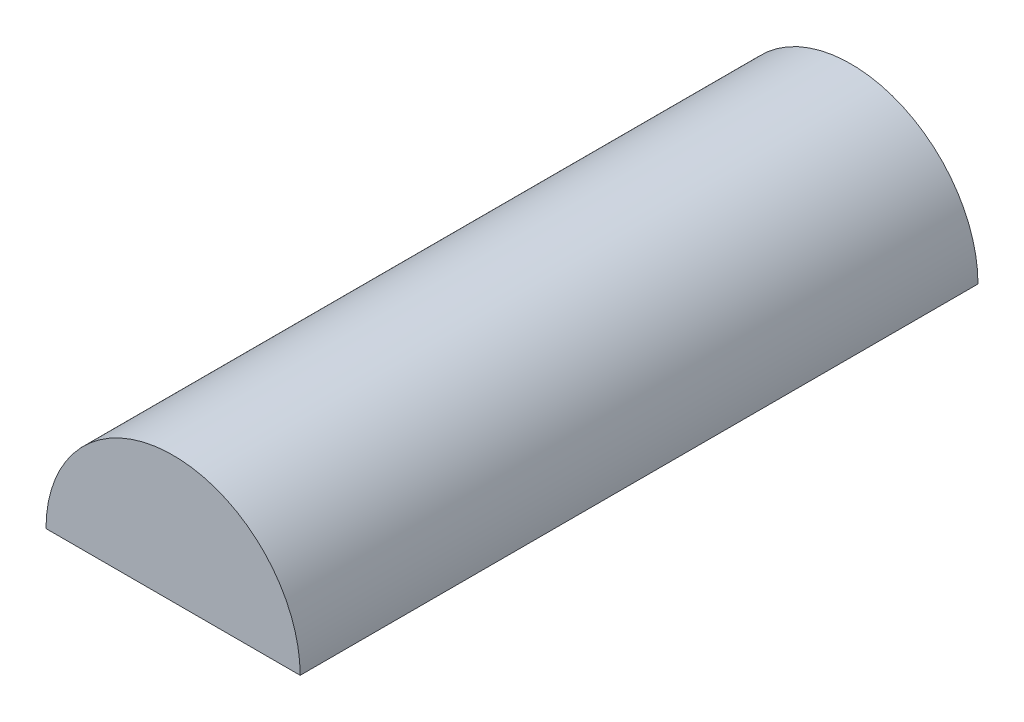
SolidWorks part; units mm, degrees
ref_plane "Front Plane" through (0, 0, 0) normal (0, 0, 1) x (1, 0, 0)
ref_plane "Top Plane" through (0, 0, 0) normal (0, 1, 0) x (1, 0, 0)
ref_plane "Right Plane" through (0, 0, 0) normal (1, 0, 0) x (0, 0, -1)
sketch "Sketch1" plane through (0, 0, 0) normal (0, 0, 1) x (1, 0, 0)
  line L0 (-76.2, 0) -> (76.2, 0)
  arc A0 (-76.2, 0) -> (76.2, 0) centre (0, 0) cw
  dimension "D1" = 76.2
extrude "Boss-Extrude1" add sketch "Sketch1" along normal blind 406.4
shell "Shell1" thickness 6.35 removed face at (0, 0, 203.2)
